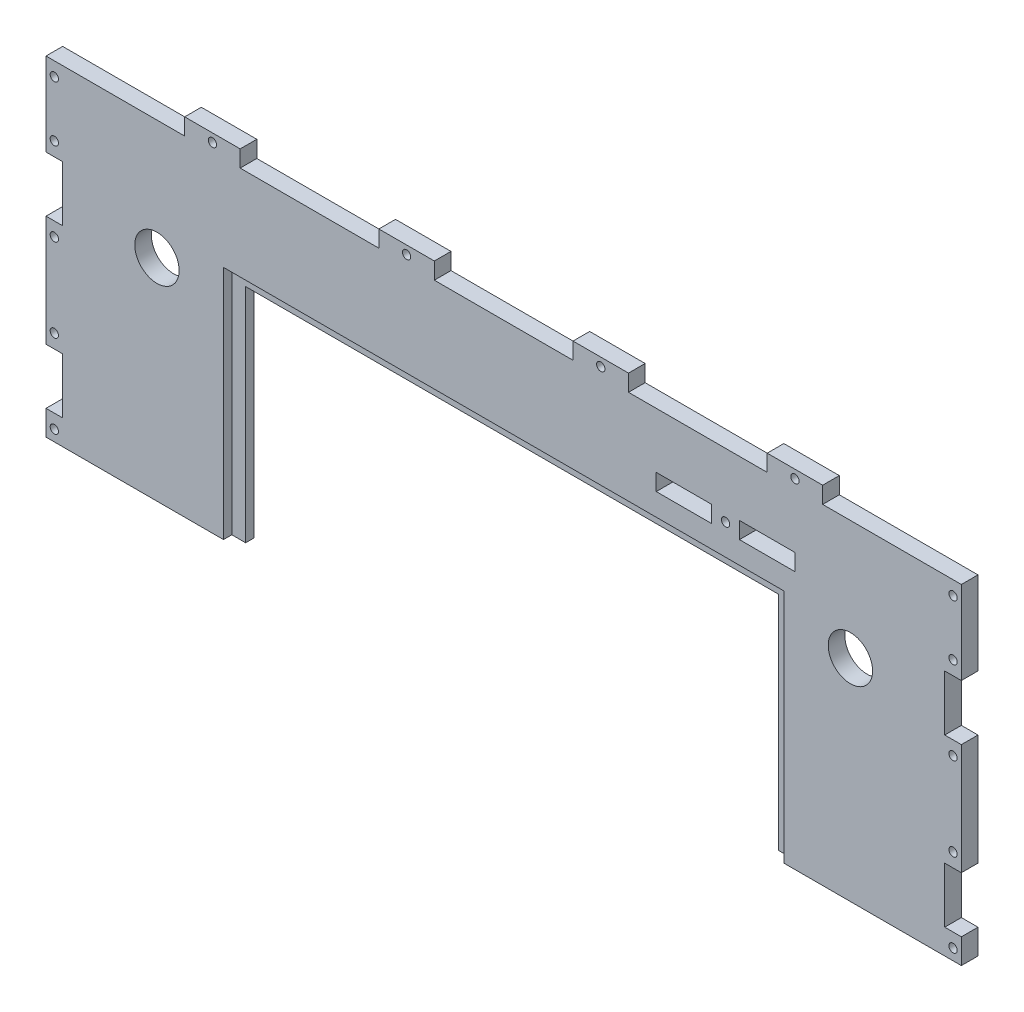
SolidWorks part; units mm, degrees
ref_plane "Plan de face" through (0, 0, 0) normal (0, 0, 1) x (1, 0, 0)
ref_plane "Plan de dessus" through (0, 0, 0) normal (0, 1, 0) x (1, 0, 0)
ref_plane "Plan de droite" through (0, 0, 0) normal (1, 0, 0) x (0, 0, -1)
sketch "Esquisse1" plane through (0, 0, 0) normal (0, 0, 1) x (1, 0, 0)
  line L0 (97.3951, 0) -> (-118.5049, 0) construction
  line L1 (-165, 119) -> (165, 119)
  line L2 (-165, 119) -> (-165, -119)
  line L3 (-165, -119) -> (165, -119)
  line L4 (165, 119) -> (165, -119)
  line L5 (0, 79.3588) -> (0, -79.3588) construction
  line L6 (-92.5, -55) -> (-77.5, -55)
  line L7 (-92.5, -55) -> (-92.5, -61)
  line L8 (-92.5, -61) -> (-77.5, -61)
  line L9 (-77.5, -55) -> (-77.5, -61)
  line L10 (-7.5, -55) -> (7.5, -55)
  line L11 (-7.5, -55) -> (-7.5, -61)
  line L12 (-7.5, -61) -> (7.5, -61)
  line L13 (7.5, -55) -> (7.5, -61)
  line L14 (77.5, -55) -> (92.5, -55)
  line L15 (77.5, -55) -> (77.5, -61)
  line L16 (77.5, -61) -> (92.5, -61)
  line L17 (92.5, -55) -> (92.5, -61)
  line L18 (-225.3679, 76) -> (203.1013, 76) construction
  line L19 (55, 99) -> (75, 99)
  line L20 (55, 99) -> (55, 93)
  line L21 (55, 93) -> (75, 93)
  line L22 (75, 99) -> (75, 93)
  line L23 (85, 99) -> (105, 99)
  line L24 (85, 99) -> (85, 93)
  line L25 (85, 93) -> (105, 93)
  line L26 (105, 99) -> (105, 93)
  circle A0 centre (-125, 76) radius 8
  circle A1 centre (125, 76) radius 8
  dimension "D23" = 16
  dimension "D24" = 16
  dimension "D1" = 238
  dimension "D2" = 330
  dimension "D3" = 165
  dimension "D4" = 119
  dimension "D5" = 15
  dimension "D6" = 6
  dimension "D7" = 6
  dimension "D8" = 15
  dimension "D9" = 6
  dimension "D10" = 15
  dimension "D11" = 70
  dimension "D12" = 70
  dimension "D13" = 58
  dimension "D14" = 72.5
  dimension "D15" = 6
  dimension "D16" = 20
  dimension "D17" = 20
  dimension "D18" = 6
  dimension "D19" = 10
  dimension "D20" = 60
  dimension "D21" = 20
  dimension "D22" = 20
  dimension "D25" = 40
  dimension "D26" = 40
  dimension "D27" = 195
extrude "Boss.-Extru.1" add sketch "Esquisse1" along normal blind 6
sketch "Esquisse2" plane through (0, 0, 6) normal (0, 0, 1) x (1, 0, 0)
  line L0 (243.146, 0) -> (-260.0003, 0) construction
  line L1 (0, 180.4713) -> (0, -129.6072) construction
  line L2 (165, 119) -> (-165, 119) construction
  line L3 (-115, 119) -> (-95, 119)
  line L4 (-115, 119) -> (-115, 125)
  line L5 (-115, 125) -> (-95, 125)
  line L6 (-95, 119) -> (-95, 125)
  line L7 (-165, 119) -> (-165, -119) construction
  line L8 (-45, 119) -> (-25, 119)
  line L9 (-45, 119) -> (-45, 125)
  line L10 (-45, 125) -> (-25, 125)
  line L11 (-25, 119) -> (-25, 125)
  line L12 (25, 119) -> (25, 125)
  line L13 (45, 125) -> (25, 125)
  line L14 (45, 119) -> (45, 125)
  line L15 (45, 119) -> (25, 119)
  line L16 (95, 119) -> (95, 125)
  line L17 (115, 125) -> (95, 125)
  line L18 (115, 119) -> (115, 125)
  line L19 (115, 119) -> (95, 119)
  line L20 (-115, 119) -> (-95, 119)
  line L21 (-115, 119) -> (-115, 125)
  line L22 (-115, 125) -> (-95, 125)
  line L23 (-95, 119) -> (-95, 125)
  line L24 (-45, 119) -> (-25, 119)
  line L25 (-45, 119) -> (-45, 125)
  line L26 (-45, 125) -> (-25, 125)
  line L27 (-25, 119) -> (-25, 125)
  line L28 (25, 119) -> (25, 125)
  line L29 (45, 125) -> (25, 125)
  line L30 (45, 119) -> (45, 125)
  line L31 (45, 119) -> (25, 119)
  line L32 (95, 119) -> (95, 125)
  line L33 (115, 125) -> (95, 125)
  line L34 (115, 119) -> (115, 125)
  line L35 (115, 119) -> (95, 119)
  line L36 (115, -119) -> (95, -119)
  line L37 (115, -119) -> (115, -125)
  line L38 (115, -125) -> (95, -125)
  line L39 (95, -119) -> (95, -125)
  line L40 (45, -119) -> (25, -119)
  line L41 (45, -119) -> (45, -125)
  line L42 (45, -125) -> (25, -125)
  line L43 (25, -119) -> (25, -125)
  line L44 (-25, -119) -> (-25, -125)
  line L45 (-45, -125) -> (-25, -125)
  line L46 (-45, -119) -> (-45, -125)
  line L47 (-45, -119) -> (-25, -119)
  line L48 (-95, -119) -> (-95, -125)
  line L49 (-115, -125) -> (-95, -125)
  line L50 (-115, -119) -> (-115, -125)
  line L51 (-115, -119) -> (-95, -119)
  line L52 (115, -119) -> (95, -119)
  line L53 (115, -119) -> (115, -125)
  line L54 (115, -125) -> (95, -125)
  line L55 (95, -119) -> (95, -125)
  line L56 (45, -119) -> (25, -119)
  line L57 (45, -119) -> (45, -125)
  line L58 (45, -125) -> (25, -125)
  line L59 (25, -119) -> (25, -125)
  line L60 (-25, -119) -> (-25, -125)
  line L61 (-45, -125) -> (-25, -125)
  line L62 (-45, -119) -> (-45, -125)
  line L63 (-45, -119) -> (-25, -119)
  line L64 (-95, -119) -> (-95, -125)
  line L65 (-115, -125) -> (-95, -125)
  line L66 (-115, -119) -> (-115, -125)
  line L67 (-115, -119) -> (-95, -119)
  line M9 (-165, -119) -> (165, -119)
  line M11 (165, 119) -> (-165, 119)
  dimension "D1" = 6
  dimension "D2" = 6
  dimension "D3" = 20
  dimension "D4" = 20
  dimension "D5" = 50
  dimension "D6" = 50
extrude "Boss.-Extru.2" add sketch "Esquisse2" against normal blind 6 contours L6 L5 L4 M11 | L11 L10 L9 M11 | L14 L13 L12 M11 | L18 L17 L16 M11 | L39 L38 L37 M9 | L43 L42 L41 M9 | L46 L45 L44 M9 | L50 L49 L48 M9 region at (-105, 122, 6) region at (105, 122, 6) region at (35, 122, 6) region at (-35, 122, 6) region at (105, -122, 6) region at (-105, -122, 6) region at (-35, -122, 6) region at (35, -122, 6)
sketch "Esquisse3" plane through (0, 0, 6) normal (0, 0, 1) x (1, 0, 0)
  line L0 (-165, 119) -> (-165, -119) construction
  line L1 (-165, 69) -> (-159, 69)
  line L2 (-165, 69) -> (-165, 89)
  line L3 (-165, 89) -> (-159, 89)
  line L4 (-159, 69) -> (-159, 89)
  line L5 (234.1368, 0) -> (-337.9213, 0) construction
  line L6 (-165, 29) -> (-159, 29)
  line L7 (-165, 29) -> (-165, 9)
  line L8 (-165, 9) -> (-159, 9)
  line L9 (-159, 29) -> (-159, 9)
  line L10 (0, 279.7488) -> (0, -188.1201) construction
  line L11 (-115, 119) -> (-165, 119) construction
  line L12 (-159, -29) -> (-159, -9)
  line L13 (-165, -9) -> (-159, -9)
  line L14 (-165, -29) -> (-165, -9)
  line L15 (-165, -29) -> (-159, -29)
  line L16 (-159, -69) -> (-159, -89)
  line L17 (-165, -89) -> (-159, -89)
  line L18 (-165, -69) -> (-165, -89)
  line L19 (-165, -69) -> (-159, -69)
  line L20 (165, -69) -> (159, -69)
  line L21 (165, -69) -> (165, -89)
  line L22 (165, -89) -> (159, -89)
  line L23 (159, -69) -> (159, -89)
  line L24 (165, -29) -> (159, -29)
  line L25 (165, -29) -> (165, -9)
  line L26 (165, -9) -> (159, -9)
  line L27 (159, -29) -> (159, -9)
  line L28 (159, 29) -> (159, 9)
  line L29 (165, 9) -> (159, 9)
  line L30 (165, 29) -> (165, 9)
  line L31 (165, 29) -> (159, 29)
  line L32 (159, 69) -> (159, 89)
  line L33 (165, 89) -> (159, 89)
  line L34 (165, 69) -> (165, 89)
  line L35 (165, 69) -> (159, 69)
  line L36 (153, -119) -> (153, -109)
  line L37 (-165, -119) -> (-153, -119)
  line L38 (-165, -119) -> (-165, -109)
  line L39 (-165, -109) -> (-153, -109)
  line L40 (-153, -119) -> (-153, -109)
  line L41 (165, -109) -> (153, -109)
  line L42 (165, -119) -> (165, -109)
  line L43 (165, -119) -> (153, -119)
  dimension "D1" = 40
  dimension "D2" = 6
  dimension "D3" = 6
  dimension "D4" = 20
  dimension "D5" = 20
  dimension "D6" = 30
  dimension "D7" = 12
  dimension "D8" = 10
extrude "Enlèv. mat.-Extru.1" cut sketch "Esquisse3" against normal blind 6
sketch "Esquisse4" plane through (0, 0, 6) normal (0, 0, 1) x (1, 0, 0)
  line L0 (-162, 122) -> (-162, -131.0602) construction
  line L1 (0, 158.5579) -> (0, -182.4489) construction
  line L2 (-115, 119) -> (-165, 119) construction
  line L3 (-106.4439, -58) -> (117.3944, -58) construction
  line L4 (-159, 89) -> (-165, 89) construction
  line L5 (-165, 119) -> (-165, 89) construction
  line L6 (-165, 69) -> (-159, 69) construction
  line L7 (-159, 29) -> (-165, 29) construction
  line L8 (-165, 9) -> (-159, 9) construction
  line L9 (-159, -9) -> (-165, -9) construction
  line L10 (-92.5, -55) -> (-92.5, -61) construction
  line L11 (-77.5, -61) -> (-77.5, -55) construction
  line L12 (-165, -29) -> (-159, -29) construction
  line L13 (-159, -69) -> (-165, -69) construction
  line L14 (-165, -89) -> (-159, -89) construction
  line L15 (-7.5, -55) -> (-7.5, -61) construction
  line L16 (162, 122) -> (162, -131.0602) construction
  line L17 (116.5184, 96) -> (43.4816, 96) construction
  line L18 (-126.5544, 122) -> (2.7821, 122) construction
  line L19 (-45, 119) -> (-95, 119) construction
  line L20 (-45, 119) -> (-45, 125) construction
  line L21 (75, 93) -> (75, 99) construction
  line L23 (55, 93) -> (75, 93) construction
  circle A0 centre (-162, 114) radius 1.5
  circle A1 centre (-162, 94) radius 1.5
  circle A2 centre (-162, 64) radius 1.5
  circle A3 centre (-162, 34) radius 1.5
  circle A4 centre (-162, 4) radius 1.5
  circle A5 centre (-105, 122) radius 1.5
  circle A6 centre (-162, -4) radius 1.5
  circle A7 centre (-162, -34) radius 1.5
  circle A8 centre (-162, -64) radius 1.5
  circle A9 centre (-162, -94) radius 1.5
  circle A10 centre (-97.5, -58) radius 1.5
  circle A11 centre (-72.5, -58) radius 1.5
  circle A12 centre (162, -94) radius 1.5
  circle A13 centre (162, -64) radius 1.5
  circle A14 centre (162, -34) radius 1.5
  circle A15 centre (162, -4) radius 1.5
  circle A16 centre (80, 96) radius 1.5
  circle A17 centre (162, 4) radius 1.5
  circle A18 centre (162, 34) radius 1.5
  circle A19 centre (162, 64) radius 1.5
  circle A20 centre (162, 94) radius 1.5
  circle A21 centre (162, 114) radius 1.5
  circle A22 centre (-12.5, -58) radius 1.5
  circle A23 centre (12.5, -58) radius 1.5
  circle A24 centre (72.5, -58) radius 1.5
  circle A25 centre (97.5, -58) radius 1.5
  circle A26 centre (-35, 122) radius 1.5
  circle A27 centre (35, 122) radius 1.5
  circle A28 centre (105, 122) radius 1.5
  dimension "D1" = 3
  dimension "D2" = 3
  dimension "D3" = 3
  dimension "D4" = 3
  dimension "D5" = 3
  dimension "D6" = 3
  dimension "D7" = 3
  dimension "D8" = 3
  dimension "D9" = 3
  dimension "D10" = 3
  dimension "D11" = 3
  dimension "D12" = 5
  dimension "D13" = 5
  dimension "D15" = 5
  dimension "D16" = 5
  dimension "D17" = 5
  dimension "D19" = 3
  dimension "D20" = 5
  dimension "D21" = 5
  dimension "D23" = 3
  dimension "D24" = 3
  dimension "D25" = 5
  dimension "D26" = 5
  dimension "D27" = 5
  dimension "D28" = 10
  dimension "D29" = 3
  dimension "D30" = 5
  dimension "D31" = 3
  dimension "D33" = 10
  dimension "D14" = 3
  dimension "D18" = 5
  dimension "D22" = 5
  dimension "D32" = 3
extrude "Enlèv. mat.-Extru.2" cut sketch "Esquisse4" against normal blind 6
sketch "Esquisse5" plane through (0, 0, 6) normal (0, 0, 1) x (1, 0, 0)
  line L1 (-200.0968, 0) -> (223.5072, 0)
  line L2 (-200.0968, 0) -> (-200.0968, -150.3561)
  line L3 (-200.0968, -150.3561) -> (223.5072, -150.3561)
  line L4 (223.5072, 0) -> (223.5072, -150.3561)
extrude "Enlèv. mat.-Extru.3" cut sketch "Esquisse5" against normal blind 6
sketch "Esquisse6" plane through (0, 0, 6) normal (0, 0, 1) x (1, 0, 0)
  line L0 (-165, 69) -> (-165, 29) construction
  line L2 (165, 0) -> (-165, 0) construction
  text T0 "SUDRIABOTIK" font "Century Gothic" height in points 72
  dimension "D1" = 83.5
  dimension "D2" = 29.5
extrude "Enlèv. mat.-Extru.4" cut sketch "Esquisse6" against normal blind 6
sketch "Esquisse7" plane through (0, 0, 6) normal (0, 0, 1) x (1, 0, 0)
  line L0 (-42.8696, 29.5) -> (-48.7731, 29.5) construction
  line L1 (-44.3875, 29.5) -> (-45.9701, 29.5)
  line L2 (-44.3875, 29.5) -> (-44.3875, 31.4538)
  line L3 (-44.3875, 31.4538) -> (-45.9701, 31.4538)
  line L4 (-45.9701, 29.5) -> (-45.9701, 31.4538)
  line L5 (-47.0635, 31.4538) -> (-44.8768, 31.4538) construction
  line L6 (-23.9531, 46.5962) -> (-27.525, 46.5962) construction
  line L7 (-45.1788, 46.5937) -> (-43.5909, 46.5937)
  line L8 (-45.1788, 46.5937) -> (-45.1788, 48.5305)
  line L9 (-45.1788, 48.5305) -> (-43.5909, 48.5305)
  line L10 (-43.5909, 46.5937) -> (-43.5909, 48.5305)
  line L11 (-26.3286, 46.5962) -> (-25.4223, 46.5962)
  line L12 (-26.3286, 46.5962) -> (-26.3286, 48.55)
  line L13 (-26.3286, 48.55) -> (-25.4223, 48.55)
  line L14 (-25.4223, 46.5962) -> (-25.4223, 48.55)
  line L15 (-27.525, 46.5962) -> (-27.525, 40.2462) construction
  line L16 (-27.525, 43.4212) -> (-29.2346, 43.4212)
  line L17 (-27.525, 43.4212) -> (-27.525, 42.4505)
  line L18 (-27.525, 42.4505) -> (-29.2346, 42.4505)
  line L19 (-29.2346, 43.4212) -> (-29.2346, 42.4505)
  line L20 (-29.2346, 29.5) -> (-29.2346, 48.55) construction
  line L21 (-2.2967, 37.5596) -> (4.5112, 37.5596) construction
  line L22 (0.6712, 37.5596) -> (1.8879, 37.5596)
  line L23 (0.6712, 37.5596) -> (0.6712, 35.6058)
  line L24 (0.6712, 35.6058) -> (1.8879, 35.6058)
  line L25 (1.8879, 37.5596) -> (1.8879, 35.6058)
  line L26 (5.4118, 35.6058) -> (-3.224, 35.6058) construction
  line L27 (15.2154, 46.5962) -> (15.2154, 40.4904) construction
  line L28 (15.2154, 43.5433) -> (13.5058, 43.5433)
  line L29 (15.2154, 43.5433) -> (15.2154, 40.4904)
  line L30 (15.2154, 40.4904) -> (13.5058, 40.4904)
  line L31 (13.5058, 43.5433) -> (13.5058, 40.4904)
  line L32 (13.5058, 29.5) -> (13.5058, 48.55) construction
  line L33 (15.2154, 38.5365) -> (15.2154, 31.4538) construction
  line L34 (15.2154, 32.964) -> (13.5058, 32.964)
  line L35 (15.2154, 32.964) -> (15.2154, 35.6058)
  line L36 (15.2154, 35.6058) -> (13.5058, 35.6058)
  line L37 (13.5058, 32.964) -> (13.5058, 35.6058)
  line L39 (29.3929, 39.4529) -> (27.6822, 39.4529)
  line L40 (29.3929, 39.4529) -> (29.3929, 38.5462)
  line L41 (29.3929, 38.5462) -> (27.6822, 38.5462)
  line L42 (27.6822, 39.4529) -> (27.6822, 38.5462)
  line L43 (45.9733, 39.5873) -> (47.6814, 39.5873)
  line L44 (45.9733, 39.5873) -> (45.9733, 38.4818)
  line L45 (45.9733, 38.4818) -> (47.6814, 38.4818)
  line L46 (47.6814, 39.5873) -> (47.6814, 38.4818)
  spline S0 degree 3 poles (-39.8701, 46.0619) (-40.0299, 46.1061) (-40.3695, 46.2) (-40.9238, 46.3025) (-41.5477, 46.3928) (-42.2438, 46.4694) (-43.0115, 46.5243) (-43.8512, 46.5655) (-44.7634, 46.5933) (-45.3958, 46.5952) (-45.724, 46.5962) knots 0 0 0 0 0.084319 0.179285 0.286583 0.405111 0.535593 0.67819 0.832976 1 1 1 1 construction
  spline S1 degree 3 poles (-44.9264, 48.55) (-44.5919, 48.5476) (-43.9455, 48.5429) (-43.0114, 48.5134) (-42.1472, 48.4612) (-41.3556, 48.3852) (-40.6345, 48.2918) (-39.986, 48.1748) (-39.4066, 48.0366) (-39.0502, 47.9188) (-38.8817, 47.8631) knots 0 0 0 0 0.164289 0.317406 0.458844 0.589367 0.707831 0.81577 0.91288 1 1 1 1 construction
  spline S2 degree 3 poles (37.6465, 47.0846) (37.4657, 47.0824) (37.1058, 47.078) (36.5709, 47.0202) (36.043, 46.9379) (35.522, 46.8204) (35.0101, 46.6604) (34.5026, 46.4762) (34.004, 46.2518) (33.516, 45.9983) (33.0429, 45.7178) (32.5966, 45.4077) (32.1757, 45.0754) (31.7814, 44.72) (31.4148, 44.3398) (31.0687, 43.9406) (30.757, 43.5108) (30.4714, 43.0623) (30.2157, 42.5955) (29.9884, 42.1154) (29.8024, 41.618) (29.6508, 41.1088) (29.5251, 40.5886) (29.4454, 40.0534) (29.387, 39.5058) (29.3829, 39.1358) (29.3808, 38.9487) knots 0 0 0 0 0.042023 0.083645 0.124984 0.166247 0.207702 0.249631 0.291742 0.334743 0.37746 0.419556 0.461044 0.502096 0.542891 0.583801 0.624864 0.666225 0.707399 0.748557 0.789655 0.83074 0.87207 0.913993 0.956498 1 1 1 1 construction
  spline S3 degree 3 poles (37.7151, 29.0115) (37.3699, 29.02) (36.6894, 29.0366) (35.6905, 29.1791) (34.731, 29.4019) (33.8138, 29.7204) (32.9384, 30.132) (32.1029, 30.6338) (31.3109, 31.2293) (30.5688, 31.9051) (29.8898, 32.6409) (29.2979, 33.4292) (28.7959, 34.2546) (28.3857, 35.1195) (28.0609, 36.0196) (27.8394, 36.9609) (27.6961, 37.9381) (27.6795, 38.6034) (27.6712, 38.941) knots 0 0 0 0 0.065819 0.129747 0.192072 0.253459 0.31457 0.37628 0.439026 0.503267 0.567493 0.629705 0.691 0.751452 0.812004 0.87315 0.935635 1 1 1 1 construction
  spline S4 degree 3 poles (45.9885, 39.0364) (45.9863, 39.221) (45.9819, 39.5872) (45.9246, 40.1286) (45.8424, 40.6579) (45.7239, 41.1732) (45.5713, 41.6744) (45.383, 42.1613) (45.161, 42.6355) (44.9062, 43.0959) (44.6199, 43.5378) (44.3069, 43.9601) (43.962, 44.3551) (43.595, 44.7325) (43.1968, 45.0842) (42.7691, 45.4104) (42.3171, 45.7188) (41.8385, 45.9971) (41.3446, 46.2541) (40.8378, 46.4743) (40.3238, 46.6613) (39.804, 46.8209) (39.274, 46.9374) (38.7373, 47.0203) (38.1947, 47.078) (37.8298, 47.0824) (37.6465, 47.0846) knots 0 0 0 0 0.042915 0.08513 0.126473 0.167453 0.207976 0.248249 0.28875 0.32967 0.370537 0.411129 0.451819 0.492406 0.533486 0.575263 0.617441 0.660672 0.70394 0.746868 0.789079 0.831104 0.873238 0.915166 0.957381 1 1 1 1 construction
  spline S5 degree 3 poles (47.6981, 39.0326) (47.6896, 38.69) (47.673, 38.0145) (47.5306, 37.0231) (47.3072, 36.0702) (46.9883, 35.1571) (46.5788, 34.2831) (46.0745, 33.4504) (45.4805, 32.6588) (44.8044, 31.9169) (44.0675, 31.2365) (43.277, 30.6437) (42.4508, 30.1336) (41.5783, 29.7265) (40.6709, 29.4012) (39.7207, 29.1794) (38.732, 29.0363) (38.0578, 29.0199) (37.7151, 29.0115) knots 0 0 0 0 0.065227 0.128569 0.19032 0.251378 0.312388 0.373789 0.436431 0.500567 0.564687 0.627136 0.688455 0.749246 0.810155 0.871671 0.934773 1 1 1 1 construction
  spline S6 degree 3 poles (29.3808, 38.9487) (29.3877, 38.6735) (29.4014, 38.1321) (29.5209, 37.3387) (29.705, 36.5762) (29.9763, 35.8488) (30.3157, 35.1502) (30.7349, 34.4867) (31.2316, 33.858) (31.7959, 33.2686) (32.4127, 32.7306) (33.0676, 32.2584) (33.7537, 31.8588) (34.4727, 31.5333) (35.2208, 31.2753) (36.0029, 31.0986) (36.8136, 30.9822) (37.3662, 30.9711) (37.6465, 30.9654) knots 0 0 0 0 0.064504 0.126899 0.187747 0.24815 0.308586 0.369583 0.431827 0.49618 0.560668 0.623504 0.68526 0.746537 0.808327 0.870486 0.934317 1 1 1 1 construction
  spline S7 degree 3 poles (37.6465, 30.9654) (37.8348, 30.968) (38.2084, 30.9731) (38.7641, 31.0248) (39.3098, 31.1077) (39.8447, 31.2271) (40.3682, 31.3765) (40.8825, 31.5539) (41.3822, 31.7754) (41.8735, 32.02) (42.3437, 32.2989) (42.7926, 32.5985) (43.2089, 32.9303) (43.6029, 33.2804) (43.9709, 33.6557) (44.3106, 34.0559) (44.6208, 34.4834) (44.9063, 34.9313) (45.1611, 35.3993) (45.383, 35.8812) (45.5713, 36.3756) (45.7233, 36.8834) (45.8425, 37.4035) (45.9245, 37.9367) (45.982, 38.4819) (45.9863, 38.8506) (45.9885, 39.0364) knots 0 0 0 0 0.043633 0.086538 0.129177 0.171436 0.213416 0.255266 0.297369 0.339941 0.382347 0.423953 0.464871 0.505572 0.546003 0.586568 0.627065 0.668271 0.709549 0.750428 0.791096 0.832027 0.873136 0.914611 0.956956 1 1 1 1 construction
extrude "Boss.-Extru.5" add sketch "Esquisse7" against normal blind 6
sketch "Esquisse8" plane through (0, 0, 6) normal (0, 0, 1) x (1, 0, 0)
  line L0 (165, 0) -> (-165, 0) construction
  line L1 (-96.0144, 0) -> (96.0356, 0)
  line L2 (-96.0144, 0) -> (-96.0144, 80)
  line L3 (-96.0144, 80) -> (96.0356, 80)
  line L4 (96.0356, 0) -> (96.0356, 80)
  dimension "D1" = 192.05
  dimension "D2" = 80
  dimension "D3" = 15
extrude "Enlèv. mat.-Extru.5" cut sketch "Esquisse8" against normal blind 6 contours L2 L3 L4 L1
sketch "Esquisse11" plane through (0, 0, 6) normal (0, 0, 1) x (1, 0, 0)
  line L0 (-101.0144, 0) -> (-101.0144, 85)
  line L1 (-96.0144, 0) -> (-165, 0) construction
  line L2 (-101.0144, 85) -> (101.0356, 85)
  line L3 (101.0356, 85) -> (101.0356, 0)
  line L4 (165, 0) -> (96.0356, 0) construction
  line L5 (-96.0144, 0) -> (-96.0144, 80) construction
  line L6 (-96.0144, 80) -> (96.0356, 80) construction
  line L7 (96.0356, 0) -> (96.0356, 80) construction
  dimension "D1" = 5
  dimension "D2" = 5
  dimension "D3" = 5
extrude "Enlèv. mat.-Extru.7" cut sketch "Esquisse11" against normal blind 3 and the other way through all flip side to cut
equation "\"D3@Esquisse1\"=\"D2@Esquisse1\"/2"
equation "\"D4@Esquisse1\"=\"D1@Esquisse1\"/2"
